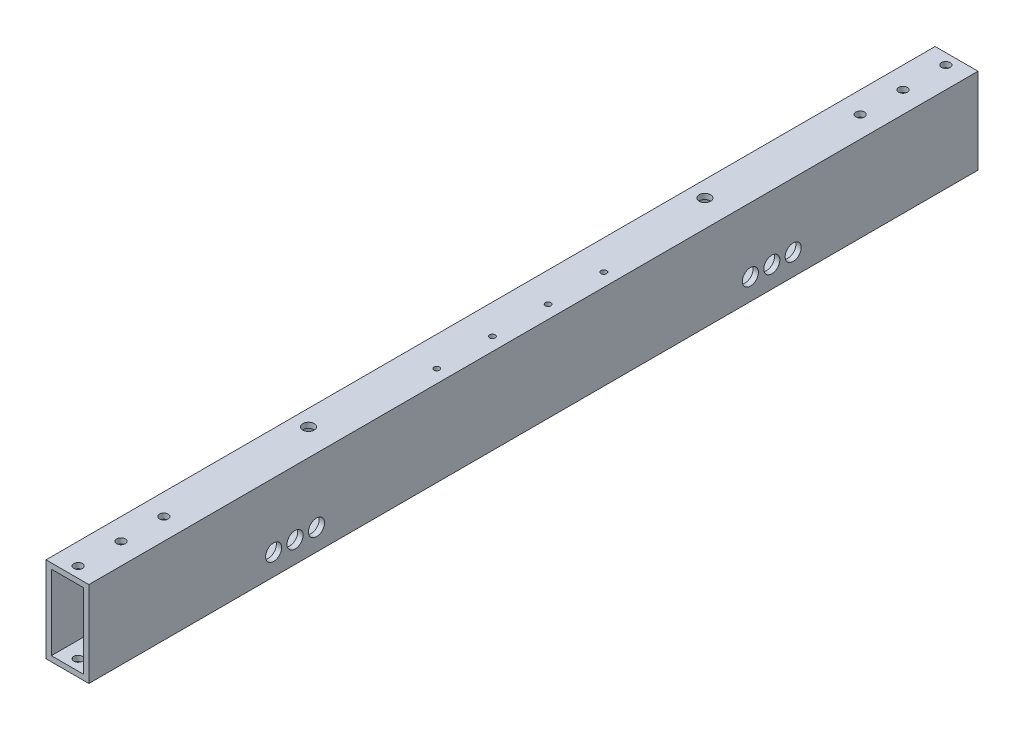
SolidWorks part; units mm, degrees
material "6061-T6 (SS)"
ref_plane "Front" through (0, 0, 0) normal (0, 0, 1) x (1, 0, 0)
ref_plane "Top" through (0, 0, 0) normal (0, 1, 0) x (1, 0, 0)
ref_plane "Right" through (0, 0, 0) normal (1, 0, 0) x (0, 0, -1)
sketch "Sketch1" plane through (0, 0, 0) normal (0, 0, 1) x (1, 0, 0)
  line L1 (-12.7, -25.4) -> (12.7, -25.4)
  line L2 (-12.7, -25.4) -> (-12.7, 25.4)
  line L3 (-12.7, 25.4) -> (12.7, 25.4)
  line L4 (12.7, -25.4) -> (12.7, 25.4)
  line L5 (-12.7, -25.4) -> (12.7, 25.4) construction
  line L6 (-12.7, 25.4) -> (12.7, -25.4) construction
  point P0 (0, 0)
  dimension "D1" = 25.4
  dimension "D2" = 50.8
extrude "Extrude-Thin1" add sketch "Sketch1" along normal blind 527.05 thin thin type one direction reverse wall 3.175
hole_wizard "#10 Clearance Hole1" positions "Sketch2" profile "Sketch3" hole size "#10" standard "ANSI Inch" end condition through all
sketch "Sketch2" plane through (0, 25.4, 0) normal (0, 1, 0) x (1, 0, 0)
  line L0 (12.7, -527.05) -> (-12.7, -527.05) construction
  line L1 (-12.7, -527.05) -> (-12.7, 0) construction
  point P0 (0, -520.7)
  point P2 (0, -495.3)
  point P4 (0, -469.9)
  point P13 (0, -6.35)
  point P15 (0, -31.75)
  point P17 (0, -57.15)
  dimension "D1" = 6.35
  dimension "D2" = 25.4
  dimension "D3" = 25.4
  dimension "D4" = 12.7
  dimension "D5" = 6.35
  dimension "D6" = 25.4
  dimension "D7" = 25.4
sketch "Sketch3" plane through (0, 25.4, 520.7) normal (1, 0, 0) x (0, 0, 1)
  line L0 (0, 0) -> (0, 50.8)
  line L1 (0, 50.8) -> (2.5527, 50.8)
  line L2 (2.5527, 50.8) -> (2.5527, 0)
  line L5 (2.5527, 0) -> (0, 0)
  line L11 (0, -6.35) -> (0, 107.95) construction
  dimension "Thru Hole Dia." = 5.1054
  dimension "Thru Hole Depth" = 50.8
sketch "Sketch8" plane through (0, -25.4, 0) normal (0, -1, 0) x (-1, 0, 0)
  point P0 (3.175, -451.358)
  point P3 (-3.175, -425.958)
  point P6 (3.175, -400.558)
  point P9 (-3.175, -375.158)
  point P12 (3.175, -349.758)
  point P19 (3.175, -298.958)
  point P26 (3.175, -248.158)
  point P29 (-3.175, -222.758)
  point P32 (3.175, -197.358)
  point P35 (-3.175, -171.958)
  point P38 (3.175, -146.558)
  point P41 (-3.175, -121.158)
  point P48 (-3.175, -70.358)
  point P55 (-3.175, -324.358)
  point P58 (-3.175, -273.558)
  point P61 (3.175, -95.758)
hole_wizard "1/8 (0.13) Diameter Hole1" positions "Sketch8" profile "Sketch7" hole size "1/8" standard "ANSI Inch" end condition up to next
sketch "Sketch7" plane through (-3.175, -25.4, 451.358) normal (1, 0, 0) x (0, 0, -1)
  line L0 (0, 0) -> (0, 3.175)
  line L1 (0, 3.175) -> (1.651, 3.175)
  line L2 (1.651, 3.175) -> (1.651, 0)
  line L5 (1.651, 0) -> (0, 0)
  line L11 (0, -6.35) -> (0, 107.95) construction
  dimension "Thru Hole Dia." = 3.302
  dimension "Thru Hole Depth" = 3.175
sketch "Sketch11" plane through (0, 25.4, 0) normal (0, 1, 0) x (1, 0, 0)
  point P0 (4.9213, -313.055)
  point P3 (4.9213, -280.035)
  point P6 (4.9213, -247.015)
  point P9 (4.9213, -213.995)
hole_wizard "1/8 (0.13) Diameter Hole2" positions "Sketch11" profile "Sketch10" hole size "1/8" standard "ANSI Inch" end condition up to next
sketch "Sketch10" plane through (4.9213, 25.4, 313.055) normal (1, 0, 0) x (0, 0, 1)
  line L0 (0, 0) -> (0, 3.175)
  line L1 (0, 3.175) -> (1.651, 3.175)
  line L2 (1.651, 3.175) -> (1.651, 0)
  line L5 (1.651, 0) -> (0, 0)
  line L11 (0, -6.35) -> (0, 107.95) construction
  dimension "Thru Hole Dia." = 3.302
  dimension "Thru Hole Depth" = 3.175
sketch "Sketch14" plane through (0, 25.4, 0) normal (0, 1, 0) x (1, 0, 0)
  line L0 (12.7, 0) -> (-12.7, 0) construction
  line L1 (12.7, -527.05) -> (-12.7, -527.05) construction
  line L2 (-12.7, -527.05) -> (-12.7, 0) construction
  point P0 (-3.175, -146.05)
  point P2 (-3.175, -381)
  dimension "D1" = 146.05
  dimension "D2" = 146.05
  dimension "D3" = 9.525
hole_wizard "1/4 Clearance Hole1" positions "Sketch14" profile "Sketch13" hole size "1/4" standard "ANSI Inch"
sketch "Sketch13" plane through (-3.175, 25.4, 146.05) normal (1, 0, 0) x (0, 0, 1)
  line L0 (0, 0) -> (0, 12.7486)
  line L1 (0, 12.7486) -> (3.3782, 10.7188)
  line L2 (3.3782, 10.7188) -> (3.3782, 0)
  line L5 (3.3782, 0) -> (0, 0)
  line L10 (0, 12.7486) -> (-3.3782, 10.7188) construction
  line L11 (0, -6.35) -> (0, 107.95) construction
  dimension "Hole Dia." = 6.7564
  dimension "Hole Depth" = 10.7188
  dimension "Drill Angle" = 118
sketch "Sketch17" plane through (12.7, 0, 0) normal (1, 0, 0) x (0, 0, -1)
  point P38 (-109.5375, -12.7)
  point P41 (-122.2375, -12.7)
  point P44 (-134.9375, -12.7)
  point P48 (-392.1125, -12.7)
  point P51 (-417.5125, -12.7)
  point P54 (-404.8125, -12.7)
hole_wizard "CBORE for #10 Socket Head Cap Screw1" positions "Sketch17" profile "Sketch16" counterbore size "#10" standard "ANSI Inch" end condition through all
sketch "Sketch16" plane through (12.7, -12.7, 109.5375) normal (0, 1, 0) x (0, 0, -1)
  line L0 (0, 0) -> (0, 25.4)
  line L1 (0, 25.4) -> (2.5527, 25.4)
  line L3 (2.5527, 25.4) -> (2.5527, 8.001)
  line L4 (2.5527, 8.001) -> (4.7625, 8.001)
  line L5 (4.7625, 8.001) -> (4.7625, 0)
  line L7 (4.7625, 0) -> (0, 0)
  line L11 (0, -6.35) -> (0, 107.95) construction
  dimension "Thru Hole Dia." = 5.1054
  dimension "Thru Hole Depth" = 25.4
  dimension "C'Bore Dia." = 9.525
  dimension "C'Bore Depth" = 8.001
